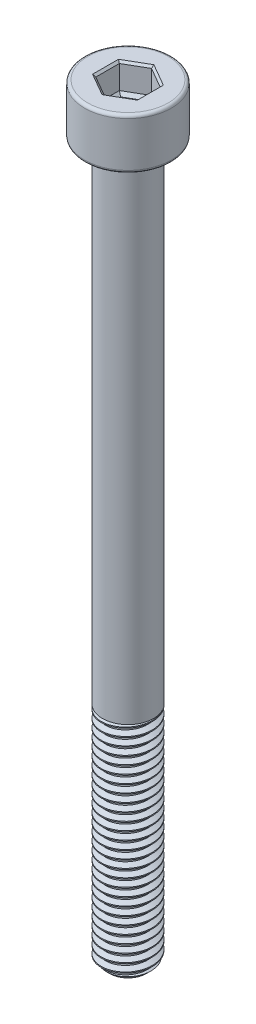
SolidWorks part; units mm, degrees
material "AISI Type A2 Tool Steel"
ref_plane "Front Plane" through (0, 0, 0) normal (0, 0, 1) x (1, 0, 0)
ref_plane "Top Plane" through (0, 0, 0) normal (0, 1, 0) x (1, 0, 0)
ref_plane "Right Plane" through (0, 0, 0) normal (1, 0, 0) x (0, 0, -1)
sketch "Sketch1" plane through (0, 0, 0) normal (0, 1, 0) x (1, 0, 0)
  circle A0 centre (0, 0) radius 2.5
  dimension "D1" = 5
extrude "Boss-Extrude1" add sketch "Sketch1" along normal blind 22
thread "Thread1" pitch 0.8 start angle 0, offset 1, length 0, pitch 0.8, diameter 5
ref_plane "Plane1" through (-2.5, 23, 0) normal (0, 0, 1) x (-1, 0, 0)
sketch "Thread Profile1" plane through (-2.5, 23, 0) normal (0, 0, 1) x (-1, 0, 0)
  line L0 (0, 0) -> (0, 0.8) construction
  line L11 (0, 0) -> (0, 0.7)
  line L12 (0, 0.7) -> (-0.433, 0.45)
  line L13 (-0.433, 0.45) -> (-0.433, 0.25)
  line L15 (-0.433, 0.25) -> (0, 0)
  line L17 (-0.433, 0.35) -> (0, 0.35) construction
  point P2 (0, 0)
  dimension "Pitch" = 0.8
  dimension "Profile_Angle" = 60
  dimension "Profile_Land" = 0.2
  dimension "Profile_Height" = 0.433
sketch "Sketch2" plane through (0, 22, 0) normal (0, 1, 0) x (1, 0, 0)
  circle A0 centre (0, 0) radius 2.5
  dimension "D1" = 5
extrude "Boss-Extrude2" add sketch "Sketch2" along normal blind 48
sketch "Sketch3" plane through (0, 70, 0) normal (0, 1, 0) x (1, 0, 0)
  circle A0 centre (0, 0) radius 4.25
  dimension "D1" = 8.5
extrude "Boss-Extrude3" add sketch "Sketch3" along normal blind 5
fillet "Fillet1" radius 0.3 2 edges at (0, 70, 4.25) (0, 75, 4.25)
sketch "Sketch4" plane through (0, 0, 0) normal (0, 0, 1) x (1, 0, 0)
  line L0 (0, 0) -> (0, 0.4416) construction
  line L1 (0, 0) -> (2.51, 0) construction
  line L2 (2.51, 0) -> (2.51, 0.7)
  line L3 (2.51, 0.7) -> (1.81, 0)
  line L4 (1.81, 0) -> (2.51, 0)
  dimension "D1" = 0.7
  dimension "D2" = 45
  dimension "D3" = 2.51
revolve "Cut-Revolve1" cut sketch "Sketch4" angle 360 about L0
sketch "Sketch5" plane through (0, 75, 0) normal (0, 1, 0) x (1, 0, 0)
  line L1 (0, 2.3094) -> (-2, 1.1547)
  line L2 (-2, 1.1547) -> (-2, -1.1547)
  line L3 (-2, -1.1547) -> (0, -2.3094)
  line L4 (0, -2.3094) -> (2, -1.1547)
  line L5 (2, -1.1547) -> (2, 1.1547)
  line L6 (2, 1.1547) -> (0, 2.3094)
  circle A0 centre (0, 0) radius 2 construction
  dimension "D1" = 4
extrude "Cut-Extrude1" cut sketch "Sketch5" against normal blind 2.5
chamfer "Chamfer1" distance 0.2 angle 45 6 edges at (-1, 75, 1.7321) (1, 75, 1.7321) (2, 75, 0) (1, 75, -1.7321) (-1, 75, -1.7321) (-2, 75, 0)
sketch "Sketch6" plane through (0, 72.5, 0) normal (0, 1, 0) x (1, 0, 0)
  line L1 (0, 2.3094) -> (-2, 1.1547)
  line L2 (-2, 1.1547) -> (-2, -1.1547)
  line L3 (-2, -1.1547) -> (0, -2.3094)
  line L4 (0, -2.3094) -> (2, -1.1547)
  line L5 (2, -1.1547) -> (2, 1.1547)
  line L6 (2, 1.1547) -> (0, 2.3094)
  circle A0 centre (0, 0) radius 2 construction
extrude "Cut-Extrude2" cut sketch "Sketch6" against normal blind 0.3 draft 45
